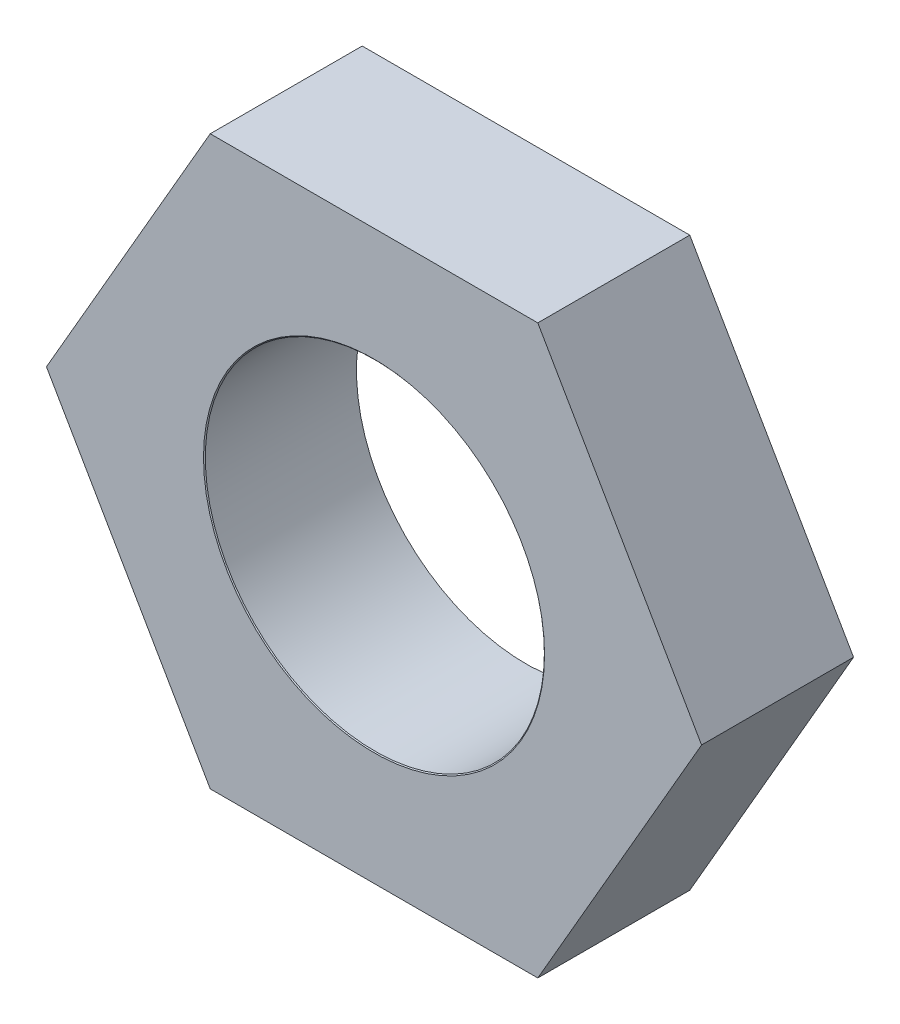
SolidWorks part; units mm, degrees
material "Stainless Steel (ferritic)"
ref_plane "Front Plane" through (0, 0, 0) normal (1, 0, 0) x (0, 1, 0)
ref_plane "Top Plane" through (0, 0, 0) normal (0, 0, 1) x (0, 1, 0)
ref_plane "Right Plane" through (0, 0, 0) normal (0, 1, 0) x (-1, 0, 0)
sketch "Sketch1" plane through (0, 0, 0) normal (0, 0, 1) x (0, 1, 0)
  line L1 (0, 8.2122) -> (-7.112, 4.1061)
  line L2 (-7.112, 4.1061) -> (-7.112, -4.1061)
  line L3 (-7.112, -4.1061) -> (0, -8.2122)
  line L4 (0, -8.2122) -> (7.112, -4.1061)
  line L5 (7.112, -4.1061) -> (7.112, 4.1061)
  line L6 (7.112, 4.1061) -> (0, 8.2122)
  circle A0 centre (0, 0) radius 5.5
  circle A1 centre (0, 0) radius 7.112 construction
  dimension "D1" = 11
  dimension "D2" = 14.224
extrude "Boss-Extrude1" add sketch "Sketch1" along normal blind 3.81 contours L5 L6 L1 L2 L3 L4 A0 | A0 region at (-5.971, 3.4474, 0) region at (0, 0, 0)
hole_wizard "Tap Drill for M10x1.5 Tap1" positions "Sketch7" profile "Sketch8" hole size "M10x1.5" standard "ANSI Metric" end condition through all
sketch "Sketch7" plane through (0, 0, 3.81) normal (0, 0, 1) x (1, 0, 0)
  point P0 (0, 0)
sketch "Sketch8" plane through (0, 0, 3.81) normal (1, 0, 0) x (0, -1, 0)
  line L0 (0, 0) -> (0, 3.81)
  line L1 (0, 3.81) -> (4.25, 3.81)
  line L2 (4.25, 3.81) -> (4.25, 0.021)
  line L3 (4.25, 0.021) -> (4.275, 0)
  line L5 (4.275, 0) -> (0, 0)
  line L6 (-4.25, 0.021) -> (-4.275, 0) construction
  line L11 (0, -6.35) -> (0, 107.95) construction
  dimension "Thru Hole Dia." = 8.5
  dimension "Thru Hole Depth" = 3.81
  dimension "Near C'Sink Dia." = 8.55
  dimension "Near C'Sink Angle" = 100
equation "\"D1@Sketch1\"=11mm"
